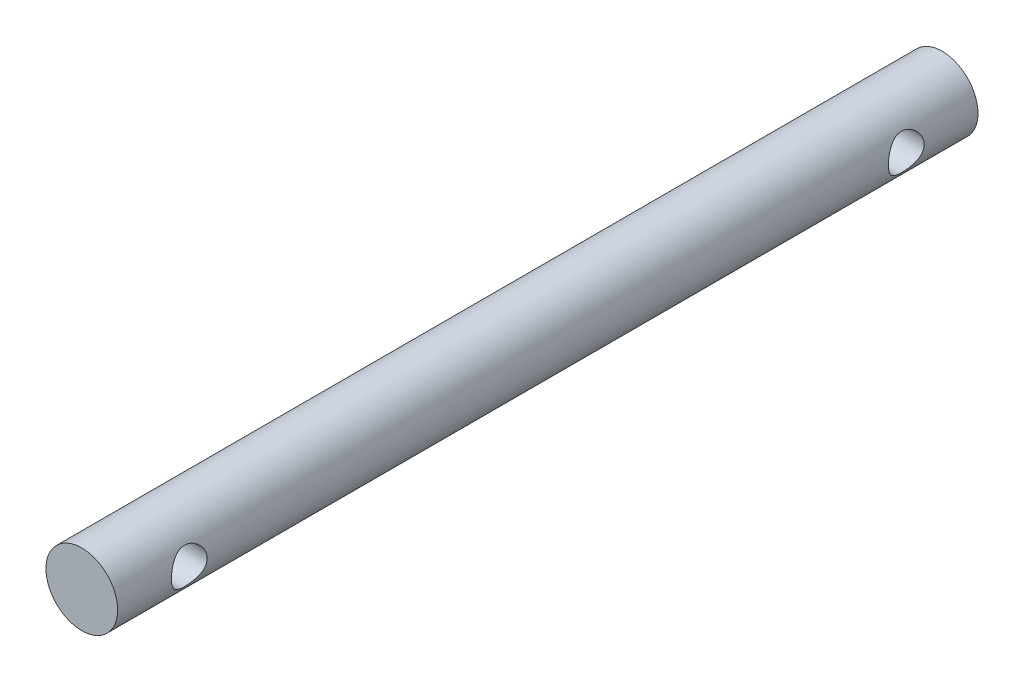
SolidWorks part; units mm, degrees
ref_plane "Plan de face" through (0, 0, 0) normal (0, 0, 1) x (1, 0, 0)
ref_plane "Plan de dessus" through (0, 0, 0) normal (0, 1, 0) x (1, 0, 0)
ref_plane "Plan de droite" through (0, 0, 0) normal (1, 0, 0) x (0, 0, -1)
sketch "Esquisse1" plane through (0, 0, 0) normal (0, 0, 1) x (1, 0, 0)
  circle A0 centre (0, 0) radius 2.5
  dimension "D1" = 5
extrude "Boss.-Extru.1" add sketch "Esquisse1" along normal blind 60
sketch "Sketch1" plane through (0, 0, 0) normal (1, 0, 0) x (0, 0, -1)
  line L1 (0, 2.5) -> (-60, 2.5) construction
  circle A0 centre (-55, 0) radius 1.25
  circle A1 centre (-5, 0) radius 1.25
  dimension "D5" = 2.5
  dimension "D6" = 2.5
  dimension "D1" = 5
  dimension "D2" = 2.5
  dimension "D3" = 2.5
  dimension "D4" = 50
extrude "Cut-Extrude1" cut sketch "Sketch1" against normal blind 10 and the other way blind 10 contours A0 | A1
